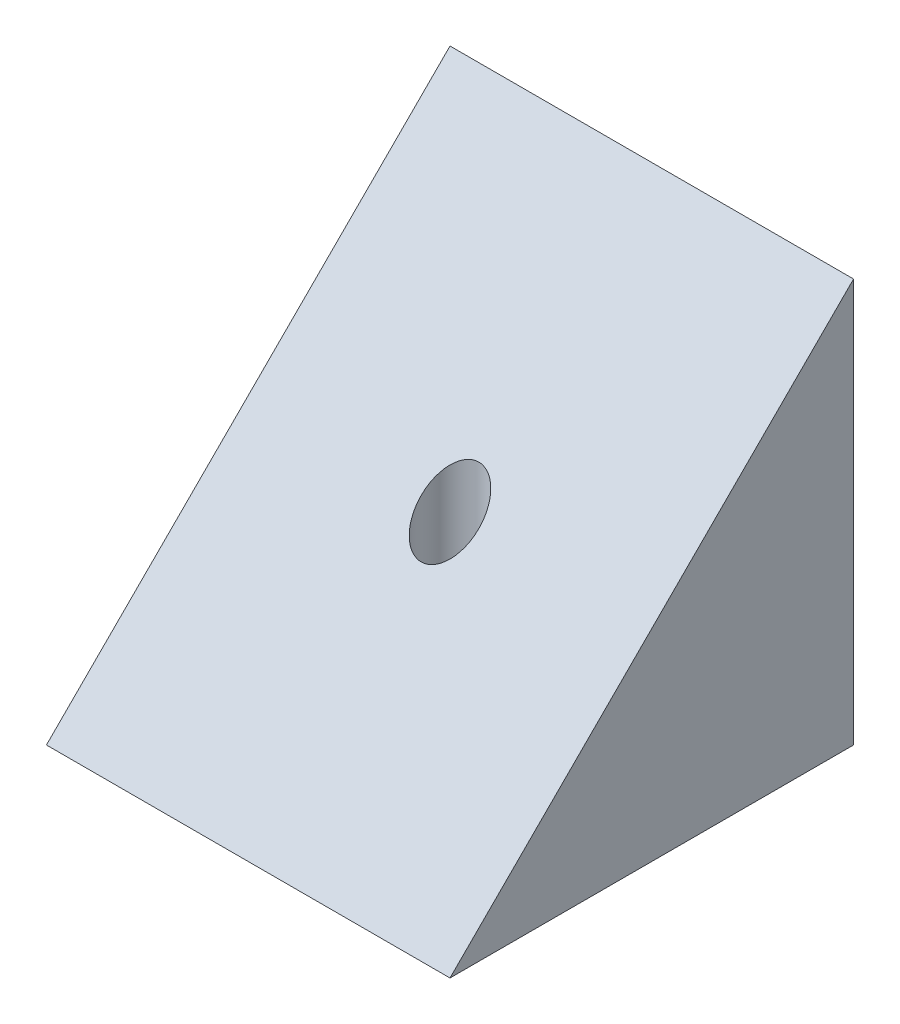
SolidWorks part; units mm, degrees
ref_plane "Face" through (0, 0, 0) normal (0, 0, 1) x (1, 0, 0)
ref_plane "Dessus" through (0, 0, 0) normal (0, 1, 0) x (1, 0, 0)
ref_plane "Droite" through (0, 0, 0) normal (1, 0, 0) x (0, 0, -1)
sketch "Esquisse1" plane through (0, 0, 0) normal (0, 0, 1) x (1, 0, 0)
  line L1 (0, 0) -> (14, 0)
  line L2 (0, 0) -> (0, 14)
  line L3 (0, 14) -> (14, 14)
  line L4 (14, 0) -> (14, 14)
  dimension "D1" = 14
  dimension "D2" = 14
extrude "Extrusion1" add sketch "Esquisse1" along normal blind 14
chamfer "Chanfrein1" distance 14 angle 45 1 edges at (7, 14, 14)
sketch "Esquisse2" plane through (0, 0, 0) normal (0, -1, 0) x (1, 0, 0)
  line L0 (0, 14) -> (14, 14) construction
  line L2 (14, 14) -> (14, 0) construction
  circle A0 centre (7, 7) radius 1
  dimension "D1" = 2
  dimension "D2" = 7
  dimension "D3" = 7
extrude "Enlèv. mat.-Extru.1" cut sketch "Esquisse2" against normal through all
